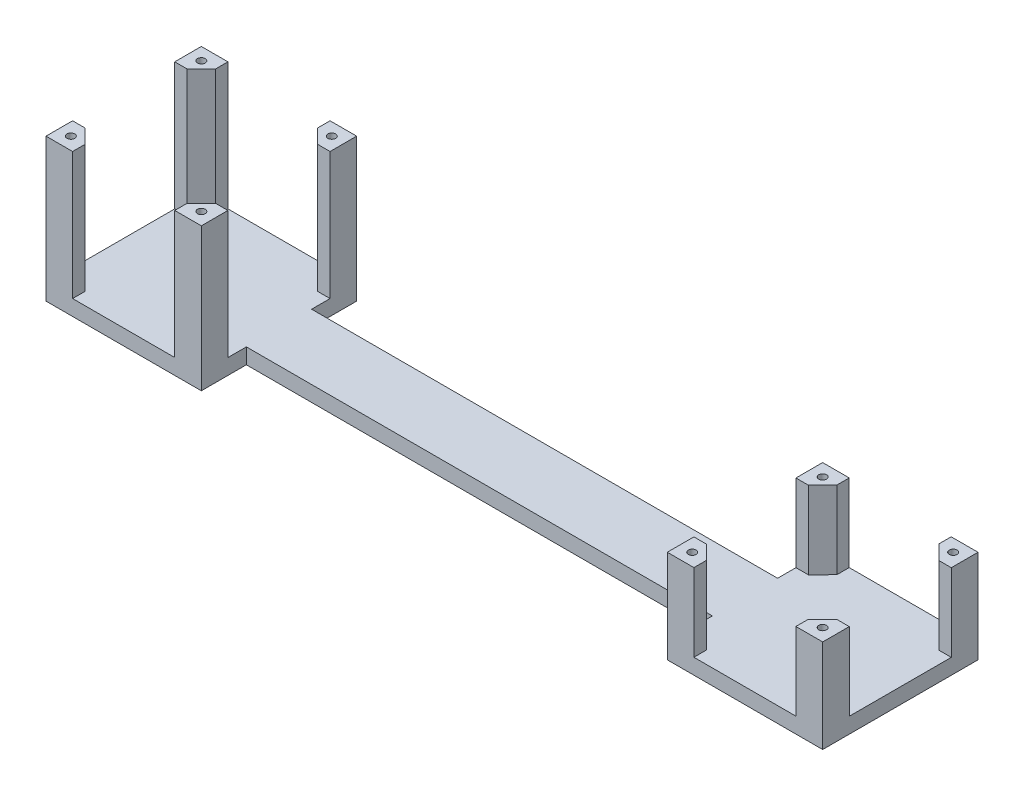
SolidWorks part; units mm, degrees
ref_plane "Front Plane" through (0, 0, 0) normal (0, 0, 1) x (1, 0, 0)
ref_plane "Top Plane" through (0, 0, 0) normal (0, 1, 0) x (1, 0, 0)
ref_plane "Right Plane" through (0, 0, 0) normal (1, 0, 0) x (0, 0, -1)
sketch "Base_sch" plane through (0, 0, 0) normal (0, 1, 0) x (1, 0, 0)
  line L5 (25, 10.5) -> (25, 25)
  line L6 (25, -25) -> (-25, -25)
  line L7 (25, 10.5) -> (175, 10.5)
  line L8 (25, -10.5) -> (175, -10.5)
  line L15 (25, -25) -> (25, -10.5)
  line L16 (25, 25) -> (-25, 25)
  line L25 (-25, -25) -> (-25, 25)
  line L28 (225.0138, -25) -> (175, -25)
  line L29 (225.0138, -25) -> (225.0138, 25)
  line L30 (225.0138, 25) -> (175, 25)
  line L31 (175, -25) -> (175, -10.5)
  line L36 (175, 10.5) -> (175, 25)
  point P0 (0, 0)
  point P1 (0, 0)
  point P8 (299.9942, 0)
  dimension "D1" = 50
  dimension "D2" = 50
  dimension "D3" = 50.0138
  dimension "D4" = 50
  dimension "D5" = 150
extrude "base_extr" add sketch "Base_sch" along normal blind 5
sketch "motor_support_sch" plane through (0, 5, 0) normal (0, 1, 0) x (1, 0, 0)
  line L0 (25, 10.5) -> (25, 25) construction
  line L5 (-25, 16.4394) -> (-25, 25)
  line L6 (-25, 25) -> (-16.4394, 25)
  line L13 (16.4394, 25) -> (25, 25)
  line L14 (25, 25) -> (25, 16.4394)
  line L15 (25, -16.4394) -> (25, -25)
  line L16 (25, -25) -> (16.4394, -25)
  line L17 (-18.7197, 18.7197) -> (-21, 16.4394)
  line L18 (-18.7197, 18.7197) -> (-16.4394, 21)
  line L19 (18.7197, 18.7197) -> (16.4394, 21)
  line L20 (18.7197, 18.7197) -> (21, 16.4394)
  line L21 (-18.7197, -18.7197) -> (-21, -16.4394)
  line L22 (-18.7197, -18.7197) -> (-16.4394, -21)
  line L23 (18.7197, -18.7197) -> (16.4394, -21)
  line L24 (18.7197, -18.7197) -> (21, -16.4394)
  line L25 (-21, 16.4394) -> (-25, 16.4394)
  line L26 (-25, 25) -> (-25, -25) construction
  line L27 (-16.4394, 21) -> (-16.4394, 25)
  line L28 (25, 25) -> (-25, 25) construction
  line L29 (16.4394, 21) -> (16.4394, 25)
  line L30 (21, 16.4394) -> (25, 16.4394)
  line L31 (-21, -16.4394) -> (-25, -16.4394)
  line L32 (-16.4394, -21) -> (-16.4394, -25)
  line L33 (-25, -25) -> (25, -25) construction
  line L34 (16.4394, -21) -> (16.4394, -25)
  line L35 (21, -16.4394) -> (25, -16.4394)
  line L36 (25, -25) -> (25, -10.5) construction
  line L37 (-25, -16.4394) -> (-25, -25)
  line L38 (-25, -25) -> (-16.4394, -25)
  point P0 (0, 0)
  point P10 (299.9942, 0)
  dimension "D7" = 41.4394
  dimension "D8" = 41.4394
extrude "Motor_1_extr" add sketch "motor_support_sch" along normal blind 41
sketch "shaft_motor_support_sch" plane through (0, 5, 0) normal (0, 1, 0) x (1, 0, 0)
  line L10 (181.2803, -18.7197) -> (179, -16.4394)
  line L11 (181.2803, -18.7197) -> (183.5606, -21)
  line L18 (179, -16.4394) -> (175, -16.4394)
  line L19 (183.5606, -21) -> (183.5606, -25)
  line L22 (175, -16.4394) -> (175, -25)
  line L23 (175, -25) -> (183.5606, -25)
  line L24 (175, 25) -> (175, 16.4025)
  line L25 (175, -24.6047) -> (175, -25)
  line L26 (175, 25) -> (175, 10.5) construction
  line L27 (175, 25) -> (183.5606, 25)
  line L28 (225.0138, -25) -> (225.0138, -16.4394)
  line L29 (225.0138, 25) -> (175, 25) construction
  line L30 (175, -10.5) -> (175, -25) construction
  line L31 (175, -25) -> (225.0138, -25) construction
  line L32 (175, 16.4025) -> (179, 16.4025)
  line L33 (183.5606, 25) -> (183.5606, 21.024)
  line L34 (183.5606, 21.024) -> (179, 16.4025)
  line L35 (225.0138, 25) -> (216.3857, 25)
  line L36 (225.0138, 25) -> (225.0138, 16.4025)
  line L37 (225.0138, -25) -> (225.0138, 25) construction
  line L38 (225.0138, 16.4025) -> (221.0566, 16.4025)
  line L39 (216.3857, 25) -> (216.3857, 21.024)
  line L40 (216.3857, 21.024) -> (221.0566, 16.4025)
  line L41 (225.0138, -25) -> (216.3857, -25)
  line L42 (216.3857, -25) -> (216.3857, -21)
  line L43 (225.0138, -16.4394) -> (221.0566, -16.4394)
  line L44 (221.0566, -16.4394) -> (216.3857, -21)
  point P0 (175, 7.9008)
  point P6 (620.659, -6.4152)
  line M11 (175, -25) -> (225.0138, -25)
  line M13 (225.0138, 25) -> (175, 25)
  dimension "D9" = 0
  dimension "D10" = 8.5606
  dimension "D11" = 4
  dimension "D12" = 3.2248
  dimension "D13" = 4
  dimension "D14" = 8.5606
  dimension "D15" = 0
extrude "shaft_motor_support_extr" add sketch "shaft_motor_support_sch" along normal blind 25 contours M13 | L18 L22 L19 L11 L10 M11 | M11 | L33 M13 region at (178.8239, 5, 21.1761) region at (221.1644, 5, 21.1848) region at (178.819, 5, -21.1622) region at (221.1693, 5, -21.1709)
hole_wizard "Tap Drill for M3x0.5 Tap1" positions "Sketch4" profile "Sketch5" hole size "M3x0.5" standard "ANSI Metric"
sketch "Sketch4" plane through (0, 46, 0) normal (0, 1, 0) x (1, 0, 0)
  point P0 (-21, -21)
  point P3 (21, -21)
  point P6 (21, 21)
  point P9 (-21, 21)
  point P12 (179.0138, 21)
  point P15 (221.0138, 21)
  point P18 (221.0138, -21)
  point P21 (179.0138, -21)
sketch "Sketch5" plane through (-21, 46, 21) normal (1, 0, 0) x (0, 0, 1)
  line L0 (0, 0) -> (0, 41.7511)
  line L1 (0, 41.7511) -> (1.25, 41)
  line L2 (1.25, 41) -> (1.25, 0)
  line L5 (1.25, 0) -> (0, 0)
  line L10 (0, 41.7511) -> (-1.25, 41) construction
  line L11 (0, -6.35) -> (0, 107.95) construction
  dimension "Hole Dia." = 2.5
  dimension "Hole Depth" = 41
  dimension "Drill Angle" = 118
